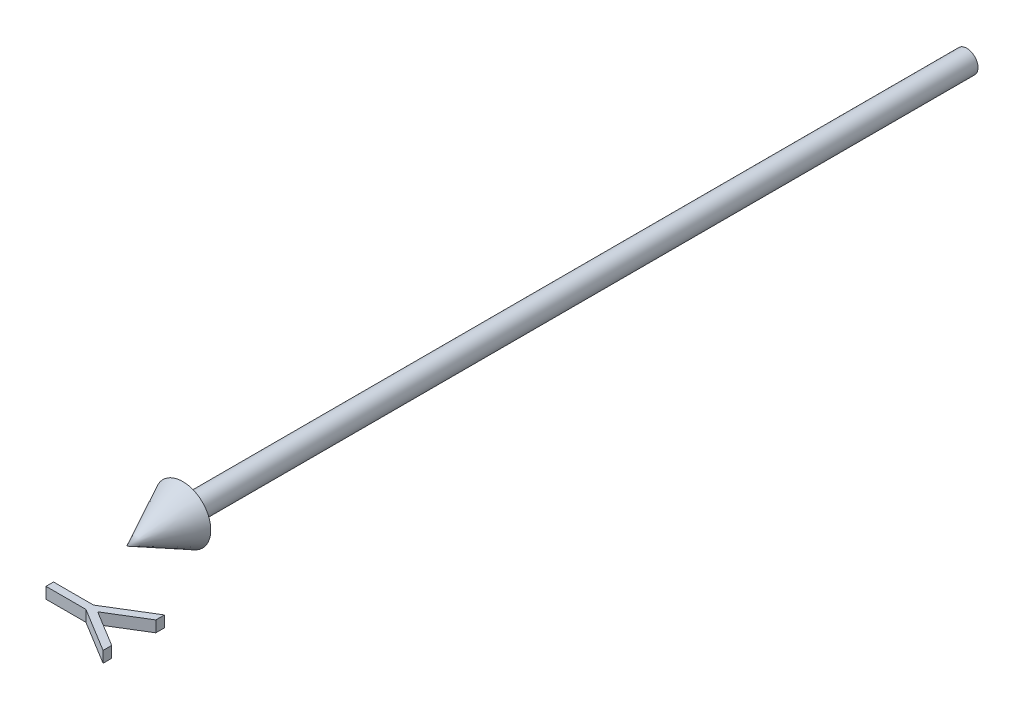
SolidWorks part; units mm, degrees
ref_plane "Front Plane" through (0, 0, 0) normal (0, 0, 1) x (1, 0, 0)
ref_plane "Top Plane" through (0, 0, 0) normal (0, 1, 0) x (1, 0, 0)
ref_plane "Right Plane" through (0, 0, 0) normal (1, 0, 0) x (0, 0, -1)
sketch "Sketch2" plane through (0, 0, 0) normal (0, 1, 0) x (1, 0, 0)
  line L0 (0, 41.95) -> (0, -114.4521) construction
  line L1 (-36.8894, 0) -> (41.4965, 0) construction
  line L2 (0, -150) -> (5, -140)
  line L3 (5, -140) -> (2, -140)
  line L4 (2, -140) -> (2, 0)
  line L5 (2, 0) -> (0, 0)
  line L6 (0, 0) -> (0, -150)
  dimension "D1" = 150
  dimension "D2" = 2
  dimension "D3" = 10
  dimension "D4" = 5
revolve "Revolve1" add sketch "Sketch2" angle 360 about L0
sketch "Sketch3" plane through (0, 0, 0) normal (0, 1, 0) x (1, 0, 0)
  line L0 (0, -157.5) -> (0, -369.2727) construction
  line L1 (-42.6057, 0) -> (45.3468, 0) construction
  text T0 "Y" font "Century Gothic" height 15
  dimension "D1" = 157.5
extrude "Boss-Extrude1" add sketch "Sketch3" against normal blind 1 and the other way blind 1 separate body
equation "\"D1@Sketch2\"=\"frame_arrow_length\""
equation "\"D2@Sketch2\"=\"frame_arrow_odA\"/2"
equation "\"D4@Sketch2\"=\"frame_arrow_head_od\""
equation "\"D3@Sketch2\"=\"frame_arrow_head_length\""
equation "\"frame_arrow_length\"=150"
equation "\"frame_arrow_head_length\"=10"
equation "\"frame_arrow_head_od\"=5"
equation "\"frame_arrow_odA\"=4"
equation "\"D1@Sketch3\"=\"frame_arrow_length\"*1.05"
